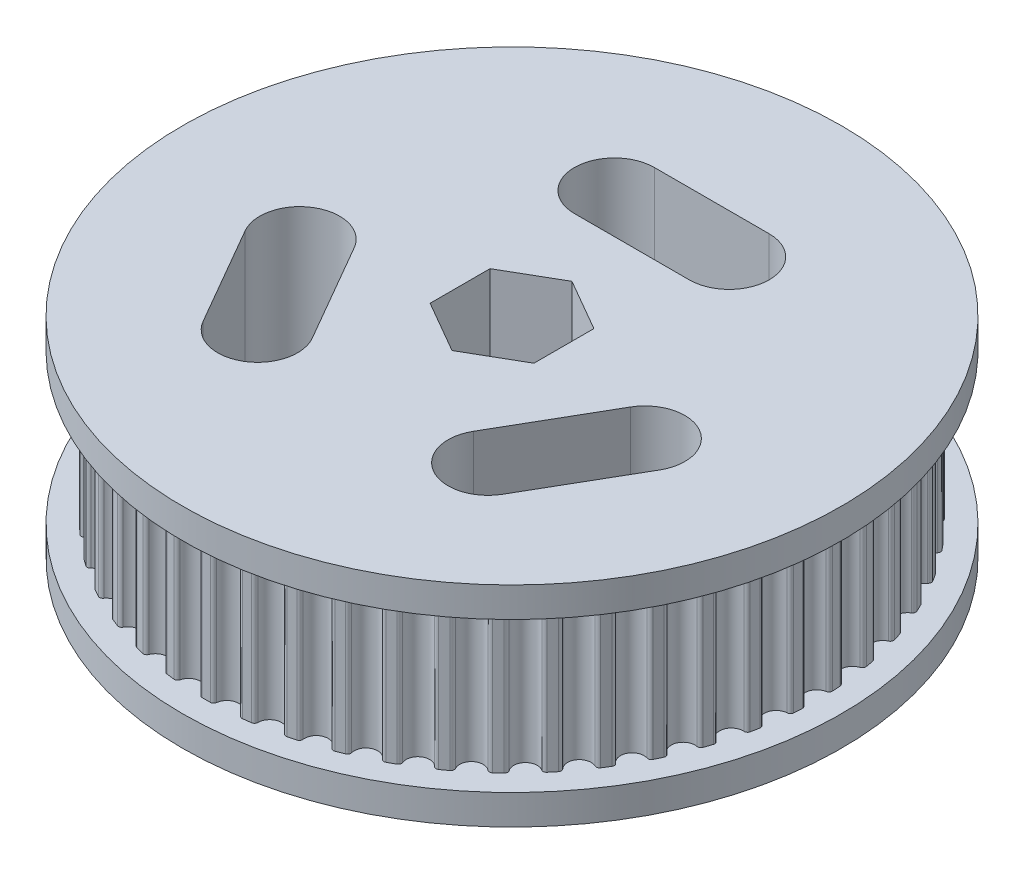
SolidWorks part; units mm, degrees
ref_plane "Front Plane" through (0, 0, 0) normal (0, 0, 1) x (1, 0, 0)
ref_plane "Top Plane" through (0, 0, 0) normal (0, 1, 0) x (1, 0, 0)
ref_plane "Right Plane" through (0, 0, 0) normal (1, 0, 0) x (0, 0, -1)
sketch "mountingHoles" plane through (0, 0, 0) normal (0, 1, 0) x (1, 0, 0)
  line L0 (-7.3025, 20.3256) -> (7.3025, 20.3256) construction
  line L1 (0, 7.6256) -> (-6.604, 3.8128)
  line L2 (-6.604, 3.8128) -> (-6.604, -3.8128)
  line L3 (-6.604, -3.8128) -> (0, -7.6256)
  line L4 (0, -7.6256) -> (6.604, -3.8128)
  line L5 (6.604, -3.8128) -> (6.604, 3.8128)
  line L6 (6.604, 3.8128) -> (0, 7.6256)
  line L15 (-7.3025, 25.4056) -> (7.3025, 25.4056)
  line L16 (-7.3025, 15.2456) -> (7.3025, 15.2456)
  line L17 (17.5529, -2.5085) -> (10.2504, -15.1568)
  line L18 (26.3517, -7.5885) -> (19.0492, -20.2368)
  line L19 (21.9523, -5.0485) -> (14.6498, -17.6968) construction
  line L20 (-10.2504, -15.1568) -> (-17.5529, -2.5085)
  line L21 (-19.0492, -20.2368) -> (-26.3517, -7.5885)
  line L22 (-14.6498, -17.6968) -> (-21.9523, -5.0485) construction
  circle A0 centre (0, 0) radius 39.751
  arc A15 (-7.3025, 25.4056) -> (-7.3025, 15.2456) centre (-7.3025, 20.3256) ccw
  circle A16 centre (0, 0) radius 6.604 construction
  arc A17 (7.3025, 15.2456) -> (7.3025, 25.4056) centre (7.3025, 20.3256) ccw
  arc A19 (26.3517, -7.5885) -> (17.5529, -2.5085) centre (21.9523, -5.0485) ccw
  arc A20 (10.2504, -15.1568) -> (19.0492, -20.2368) centre (14.6498, -17.6968) ccw
  arc A21 (-19.0492, -20.2368) -> (-10.2504, -15.1568) centre (-14.6498, -17.6968) ccw
  arc A22 (-17.5529, -2.5085) -> (-26.3517, -7.5885) centre (-21.9523, -5.0485) ccw
  point P13 (0, 20.3256)
  point P23 (18.301, -11.3727)
  point P26 (0, 0)
  point P31 (-18.301, -11.3727)
  point P36 (0, -0.8066)
  dimension "D1" = 79.502
  dimension "D2" = 13.208
  dimension "D3" = 12.7
  dimension "D4" = 5.08
  dimension "D5" = 3
  dimension "D6" = 14.605
extrude "Boss-Extrude1" add sketch "mountingHoles" along normal mid plane 19.05 contours A0
sketch "Sketch2" plane through (0, 9.525, 0) normal (0, 1, 0) x (1, 0, 0)
  line L0 (0, 0) -> (0, 39.4817) construction
  line L1 (0, 0) -> (2.4339, 38.6854) construction
  line L2 (0, 38.8874) -> (0, 39.751)
  line L3 (2.4339, 38.6854) -> (2.496, 39.6726) construction
  line L4 (4.8739, 38.5808) -> (4.9821, 39.4376)
  arc A0 (0, 38.8874) -> (0.5234, 38.8839) centre (0, 0) cw
  arc A1 (0.5234, 38.8839) -> (0.9463, 38.5043) centre (0.5176, 38.4521) cw
  arc A2 (0.9463, 38.5043) -> (3.8871, 38.3193) centre (2.4339, 38.6854) ccw
  circle A3 centre (0, 0) radius 39.751 construction
  arc A4 (4.3541, 38.6429) -> (3.8871, 38.3193) centre (4.3058, 38.2138) ccw
  arc A5 (4.8739, 38.5808) -> (4.3541, 38.6429) centre (0, 0) ccw
  arc A6 (0, 39.751) -> (4.9821, 39.4376) centre (0, 0) cw
  dimension "D3" = 0.8636
  dimension "D4" = 3.6
  dimension "D2" = 1.4986
  dimension "D1" = 0.4318
extrude "Cut-Extrude1" cut sketch "Sketch2" against normal blind 19.05 contours A6 L4 A5 A4 A2 A1 A0 L2
pattern_circular "CirPattern1" count 50 over 360 about axis through (0, 9.525, 0) along (0, -1, 0) of "Cut-Extrude1" reverse direction yes
sketch "flange" plane through (0, 9.525, 0) normal (0, 1, 0) x (1, 0, 0)
  circle A0 centre (0, 0) radius 41.91
extrude "Boss-Extrude2" add sketch "flange" along normal blind 3.81 contours A0
sketch "Sketch6" plane through (0, -9.525, 0) normal (0, -1, 0) x (1, 0, 0)
  circle A0 centre (0, 0) radius 41.91
extrude "Boss-Extrude3" add sketch "Sketch6" along normal blind 3.81
extrude "Cut-Extrude5" cut sketch "Sketch1<5>" against normal blind 31.242 and the other way blind 32.512 contours L1 L2 L3 L4 L5 L6 | L16 A17 L15 A15 | L18 A20 L17 A19 | L21 A22 L20 A21
sketch "Sketch1<5>" plane through (0, 0, 0) normal (0, 1, 0) x (1, 0, 0) same geometry as "mountingHoles"
equation "\"n\"= 50"
equation "\"p\"= 5mm"
equation "\"pd\"= \"n\" * \"p\" / 3.1415926"
